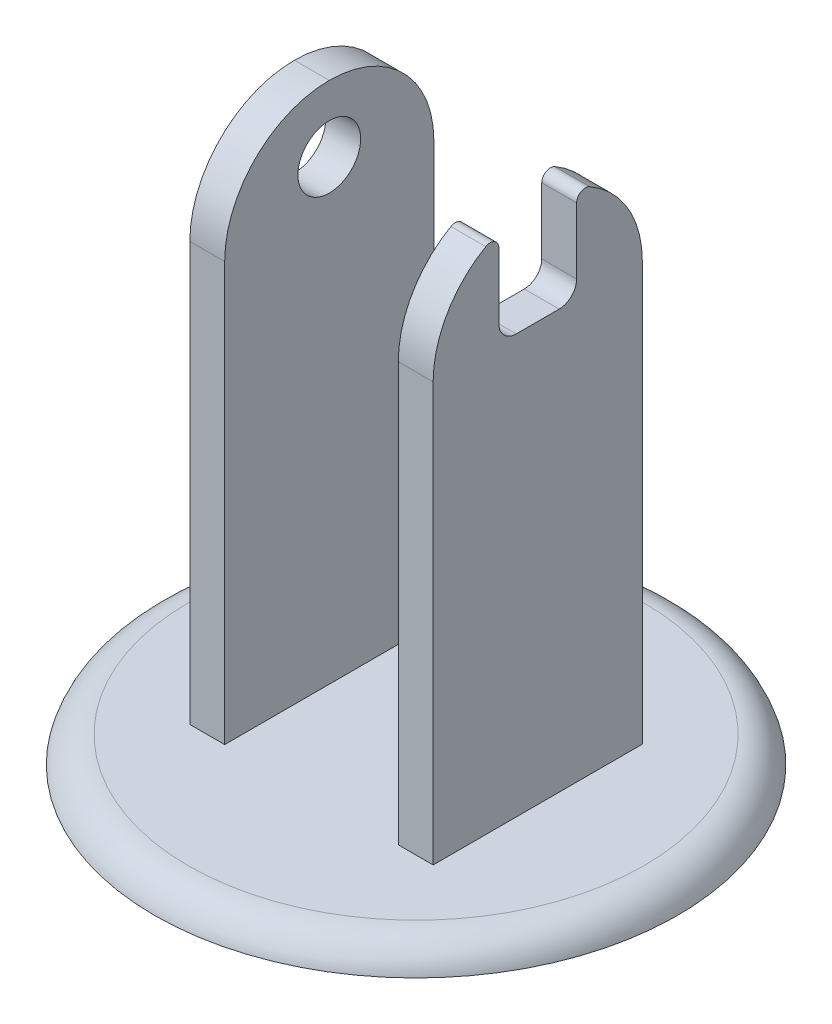
SolidWorks part; units mm, degrees
material "Cedar"
ref_plane "Front Plane" through (0, 0, 0) normal (0, 0, 1) x (1, 0, 0)
ref_plane "Top Plane" through (0, 0, 0) normal (0, 1, 0) x (1, 0, 0)
ref_plane "Right Plane" through (0, 0, 0) normal (1, 0, 0) x (0, 0, -1)
sketch "Sketch1" plane through (0, 0, 0) normal (0, 1, 0) x (1, 0, 0)
  circle A0 centre (0, 0) radius 50
extrude "Boss-Extrude1" add sketch "Sketch1" along normal blind 7.5
sketch "Sketch2" plane through (0, 7.5, 0) normal (0, 1, 0) x (1, 0, 0)
  circle A0 centre (0, 0) radius 75
extrude "Boss-Extrude2" add sketch "Sketch2" along normal blind 7.5
sketch "Sketch3" plane through (0, 15, 0) normal (0, 1, 0) x (1, 0, 0)
  line L2 (34.8963, -30) -> (24.8963, -30)
  line L3 (-34.8963, 30) -> (-24.8963, 30)
  line L4 (-34.8963, 30) -> (-34.8963, -30)
  line L5 (-34.8963, -30) -> (-24.8963, -30)
  line L6 (-24.8963, 30) -> (-24.8963, -30)
  line L7 (-34.8963, 30) -> (-24.8963, -30) construction
  line L8 (-34.8963, -30) -> (-24.8963, 30) construction
  line L9 (24.8963, 30) -> (24.8963, -30)
  line L10 (34.8963, 30) -> (24.8963, 30)
  line L11 (34.8963, 30) -> (34.8963, -30)
  point P5 (-29.8963, 0)
extrude "Boss-Extrude3" add sketch "Sketch3" along normal blind 150
fillet "Fillet1" radius 30 4 edges at (29.8963, 165, 30) (-29.8963, 165, 30) (-29.8963, 165, -30) (29.8963, 165, -30)
fillet "Fillet2" radius 10 1 edges at (0, 15, 75)
sketch "Sketch4" plane through (34.8963, 0, 0) normal (1, 0, 0) x (0, 0, -1)
  line L1 (-11.15, 195) -> (11.15, 195)
  line L2 (-11.15, 195) -> (-11.15, 140)
  line L3 (-6.15, 135) -> (6.15, 135)
  line L4 (11.15, 195) -> (11.15, 140)
  line L5 (-11.15, 195) -> (11.15, 135) construction
  line L6 (-11.15, 135) -> (11.15, 195) construction
  arc A0 (6.15, 135) -> (11.15, 140) centre (6.15, 140) ccw
  arc A1 (-6.15, 135) -> (-11.15, 140) centre (-6.15, 140) cw
  point P0 (0, 165)
  dimension "D3" = 5
  dimension "D1" = 22.3
  dimension "D2" = 60
extrude "Cut-Extrude1" cut sketch "Sketch4" against normal blind 10
fillet "Fillet3" radius 2.5 2 edges at (29.8963, 162.851, -11.15) (29.8963, 162.851, 11.15)
sketch "Sketch5" plane through (34.8963, 0, 0) normal (1, 0, 0) x (0, 0, -1)
  circle A0 centre (0, 146) radius 9
extrude "Cut-Extrude6" cut sketch "Sketch5" against normal through all
